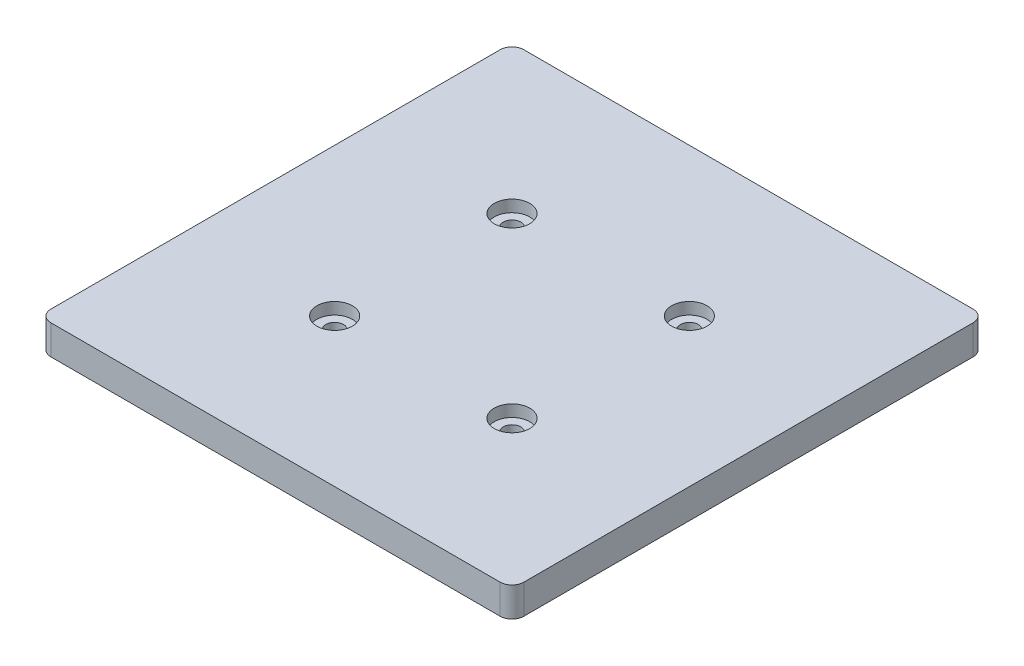
SolidWorks part; units mm, degrees
material "ABS"
ref_plane "Plan de face" through (0, 0, 0) normal (0, 0, 1) x (1, 0, 0)
ref_plane "Plan de dessus" through (0, 0, 0) normal (0, 1, 0) x (1, 0, 0)
ref_plane "Plan de droite" through (0, 0, 0) normal (1, 0, 0) x (0, 0, -1)
sketch "Esquisse1" plane through (0, 0, 0) normal (0, 1, 0) x (1, 0, 0)
  line L0 (0, 0) -> (0, 40) construction
  line L1 (-40, 40) -> (40, 40)
  line L2 (-40, 40) -> (-40, -40)
  line L3 (-40, -40) -> (40, -40)
  line L4 (40, 40) -> (40, -40)
  line L5 (0, 0) -> (40, 0) construction
  circle A0 centre (-15, 15) radius 1.5
  circle A1 centre (15, 15) radius 1.5
  circle A2 centre (-15, -15) radius 1.5
  circle A3 centre (15, -15) radius 1.5
  dimension "D4" = 3
  dimension "D1" = 80
  dimension "D2" = 15
  dimension "D3" = 15
extrude "Extrusion1" add sketch "Esquisse1" along normal blind 5
sketch "Esquisse2" plane through (0, 5, 0) normal (0, 1, 0) x (1, 0, 0)
  line L0 (0, 0) -> (0, 40) construction
  line L1 (40, 40) -> (-40, 40) construction
  line L2 (0, 0) -> (40, 0) construction
  line L3 (40, -40) -> (40, 40) construction
  circle A0 centre (-15, 15) radius 3
  circle A1 centre (15, 15) radius 3
  circle A2 centre (15, -15) radius 3
  circle A3 centre (-15, -15) radius 3
  dimension "D1" = 6
extrude "Enlèv. mat.-Extru.1" cut sketch "Esquisse2" against normal blind 2
fillet "Congé1" radius 2 4 edges at (40, 2.5, -40) (-40, 2.5, -40) (-40, 2.5, 40) (40, 2.5, 40)
